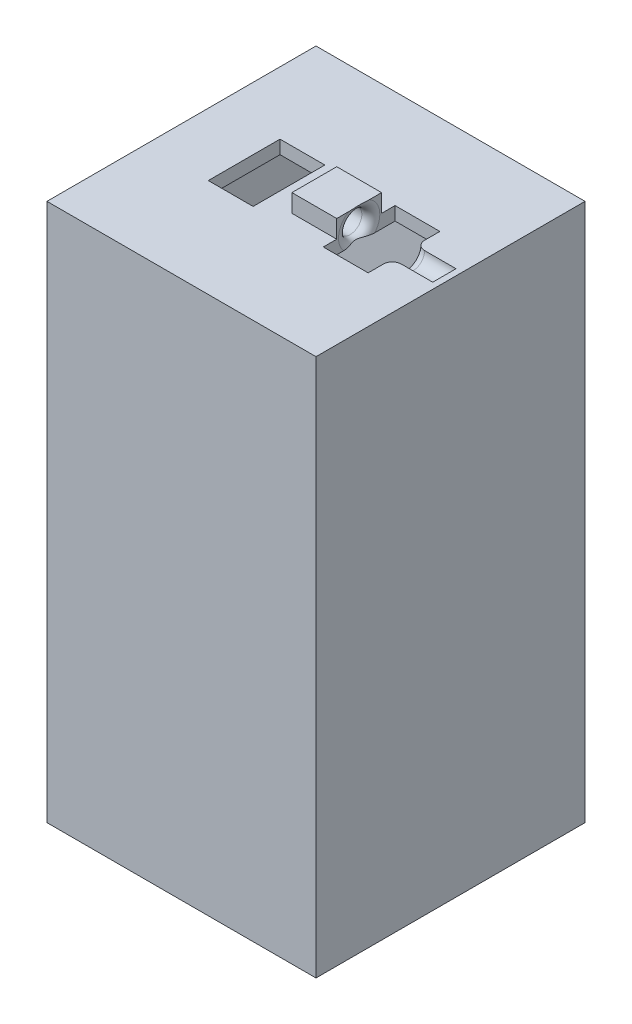
SolidWorks part; units mm, degrees
ref_plane "Front Plane" through (0, 0, 0) normal (0, 0, 1) x (1, 0, 0)
ref_plane "Top Plane" through (0, 0, 0) normal (0, 1, 0) x (1, 0, 0)
ref_plane "Right Plane" through (0, 0, 0) normal (1, 0, 0) x (0, 0, -1)
sketch "Sketch1" plane through (0, 0, 0) normal (0, 1, 0) x (1, 0, 0)
  line L1 (-38.1, -38.1) -> (38.1, -38.1)
  line L2 (-38.1, -38.1) -> (-38.1, 38.1)
  line L3 (-38.1, 38.1) -> (38.1, 38.1)
  line L4 (38.1, -38.1) -> (38.1, 38.1)
  line L5 (-38.1, -38.1) -> (38.1, 38.1) construction
  line L6 (-38.1, 38.1) -> (38.1, -38.1) construction
  point P0 (0, 0)
  dimension "D1" = 76.2
  dimension "D2" = 76.2
extrude "main body" add sketch "Sketch1" along normal blind 152.4
shell "hollow it" thickness 3.81 removed face at (0, 0, 0)
sketch "Sketch2" plane through (0, 152.4, 0) normal (0, 1, 0) x (1, 0, 0)
  line L1 (24.9265, 10.16) -> (12.2265, 10.16)
  line L2 (24.9265, 10.16) -> (24.9265, -10.16)
  line L3 (24.9265, -10.16) -> (12.2265, -10.16)
  line L4 (12.2265, 10.16) -> (12.2265, -10.16)
  line L5 (24.9265, 10.16) -> (12.2265, -10.16) construction
  line L6 (24.9265, -10.16) -> (12.2265, 10.16) construction
  line L7 (-7.6512, -10.16) -> (-20.3512, -10.16)
  line L8 (-7.6512, -10.16) -> (-7.6512, 10.16)
  line L9 (-7.6512, 10.16) -> (-20.3512, 10.16)
  line L10 (-20.3512, -10.16) -> (-20.3512, 10.16)
  line L11 (-7.6512, -10.16) -> (-20.3512, 10.16) construction
  line L12 (-7.6512, 10.16) -> (-20.3512, -10.16) construction
  point P0 (18.5765, 0)
  point P5 (-14.0012, 0)
  dimension "D1" = 20.32
  dimension "D2" = 12.7
  dimension "D3" = 20.32
  dimension "D4" = 12.7
extrude "base holes for both" cut sketch "Sketch2" against normal up to next
ref_plane "arm guys plane" through (12.2265, 0, 0) normal (1, 0, 0) x (0, 0, -1)
sketch "Sketch3" plane through (12.2265, 0, 0) normal (1, 0, 0) x (0, 0, -1)
  line L0 (0, 152.4) -> (6.35, 152.4)
  line L1 (10.16, 152.4) -> (-10.16, 152.4) construction
  line L2 (6.35, 152.4) -> (6.35, 157.48)
  line L3 (6.35, 157.48) -> (-6.35, 157.48)
  line L4 (-6.35, 157.48) -> (-6.35, 152.4)
  line L5 (-6.35, 152.4) -> (0, 152.4)
  dimension "D1" = 6.35
  dimension "D2" = 6.35
  dimension "D3" = 5.08
extrude "nibble base hole" add sketch "Sketch3" against normal blind 12.7
ref_point "nibble base point"
sketch "Sketch5" plane through (12.2265, 0, 0) normal (1, 0, 0) x (0, 0, -1)
  circle A0 centre (0, 152.4) radius 3.302
extrude "nibble hole" cut sketch "Sketch5" against normal blind 11.43 and the other way blind 24.13
fillet "easy to insert scroll wheel" radius 2.54 2 edges at (24.9265, 149.098, 0) (12.2265, 152.4, 3.302)
